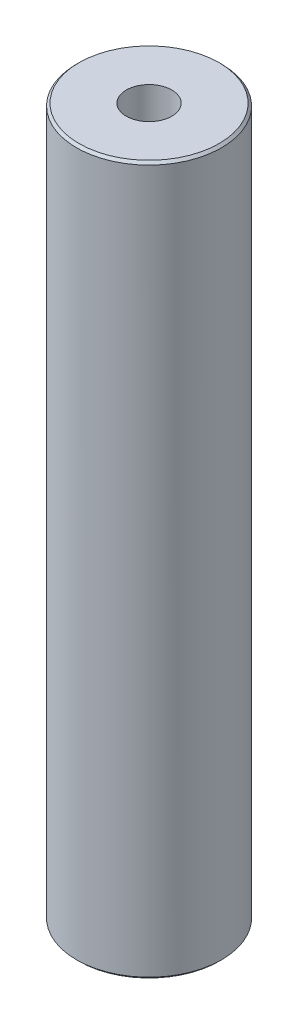
SolidWorks part; units mm, degrees
ref_plane "Front Plane" through (0, 0, 0) normal (0, 0, 1) x (1, 0, 0)
ref_plane "Top Plane" through (0, 0, 0) normal (0, 1, 0) x (1, 0, 0)
ref_plane "Right Plane" through (0, 0, 0) normal (1, 0, 0) x (0, 0, -1)
sketch "Sketch1" plane through (0, 0, 0) normal (0, 1, 0) x (1, 0, 0)
  circle A0 centre (0, 0) radius 40
  dimension "SHAFT_OD" = 80
extrude "Boss-Extrude1" add sketch "Sketch1" along normal blind 390.6401
sketch "Sketch2" plane through (0, 0, 0) normal (0, 1, 0) x (1, 0, 0)
  circle A0 centre (0, 0) radius 12.5528
  dimension "BORE_D" = 25.1055
extrude "Cut-Extrude1" cut sketch "Sketch2" along normal through all
chamfer "Chamfer1" distance 1.3548 angle 45 2 edges at (0, 390.6401, 40) (0, 0, 40)
